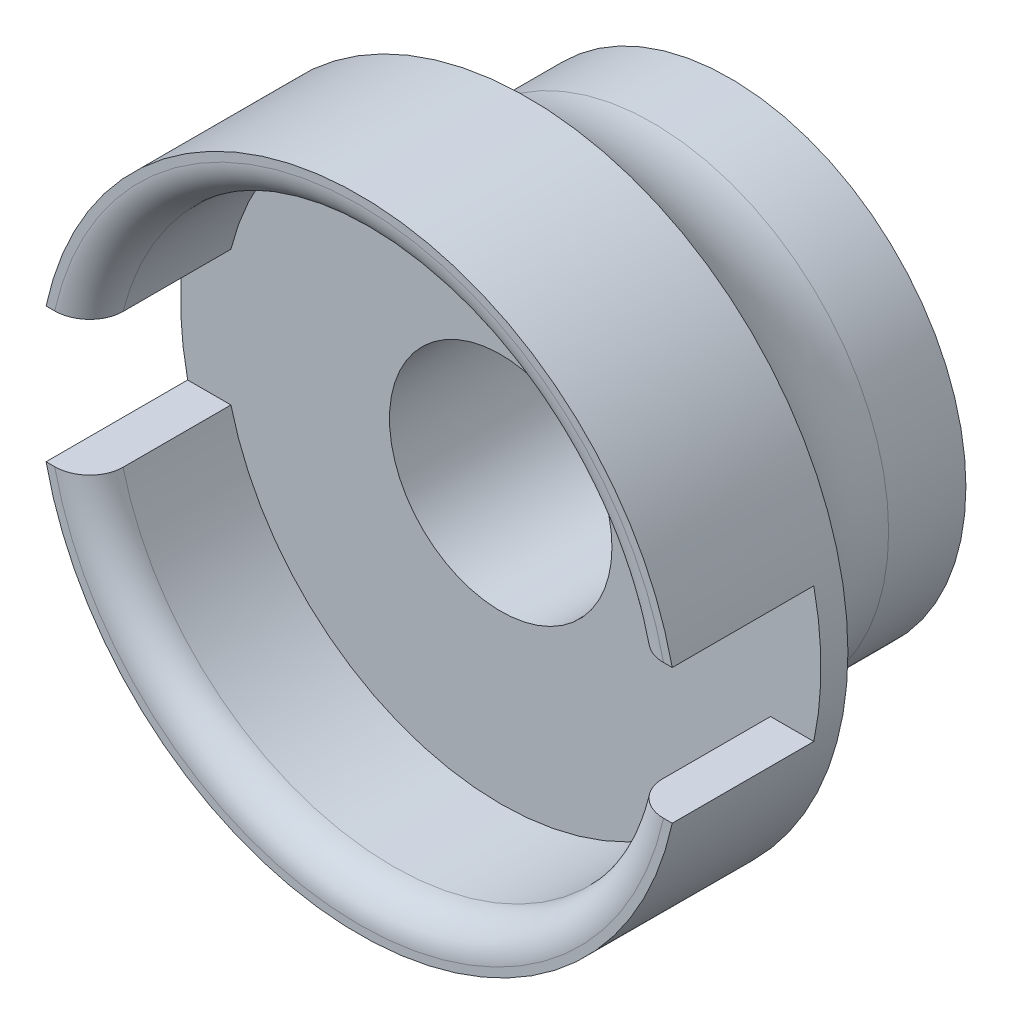
SolidWorks part; units mm, degrees
ref_plane "Front Plane" through (0, 0, 0) normal (0, 0, 1) x (1, 0, 0)
ref_plane "Top Plane" through (0, 0, 0) normal (0, 1, 0) x (1, 0, 0)
ref_plane "Right Plane" through (0, 0, 0) normal (1, 0, 0) x (0, 0, -1)
sketch "Sketch1" plane through (0, 0, 0) normal (0, 0, 1) x (1, 0, 0)
  circle A0 centre (0, 0) radius 1.65
  circle A1 centre (0, 0) radius 3.5
  dimension "D1" = 3.3
  dimension "D2" = 7
extrude "Boss-Extrude1" add sketch "Sketch1" along normal blind 1 and the other way blind 2
sketch "Sketch2" plane through (0, 0, 1) normal (0, 0, 1) x (1, 0, 0)
  circle A0 centre (0, 0) radius 4.75
  dimension "D1" = 9.5
extrude "Boss-Extrude2" add sketch "Sketch2" along normal blind 2.5
sketch "Sketch3" plane through (0, 0, 3.5) normal (0, 0, 1) x (1, 0, 0)
  circle A0 centre (0, 0) radius 4.125
  dimension "D1" = 8.25
extrude "Cut-Extrude1" cut sketch "Sketch3" against normal blind 2.1
fillet "Fillet1" radius 0.5 1 edges at (4.125, 0, 3.5)
sketch "Sketch4" plane through (0, 0, -2) normal (0, 0, -1) x (-1, 0, 0)
  circle A0 centre (0, 0) radius 1.65
extrude "Cut-Extrude2" cut sketch "Sketch4" against normal blind 10
sketch "Sketch5" plane through (0, 0, 1.4) normal (0, 0, 1) x (1, 0, 0)
  line L1 (-7.5567, 1) -> (7.5567, 1)
  line L2 (-7.5567, 1) -> (-7.5567, -1)
  line L3 (-7.5567, -1) -> (7.5567, -1)
  line L4 (7.5567, 1) -> (7.5567, -1)
  line L5 (-7.5567, 1) -> (7.5567, -1) construction
  line L6 (-7.5567, -1) -> (7.5567, 1) construction
  point P0 (0, 0)
  dimension "D1" = 2
extrude "Cut-Extrude3" cut sketch "Sketch5" along normal blind 3
fillet "Fillet2" radius 2 1 edges at (3.5, 0, 1)
